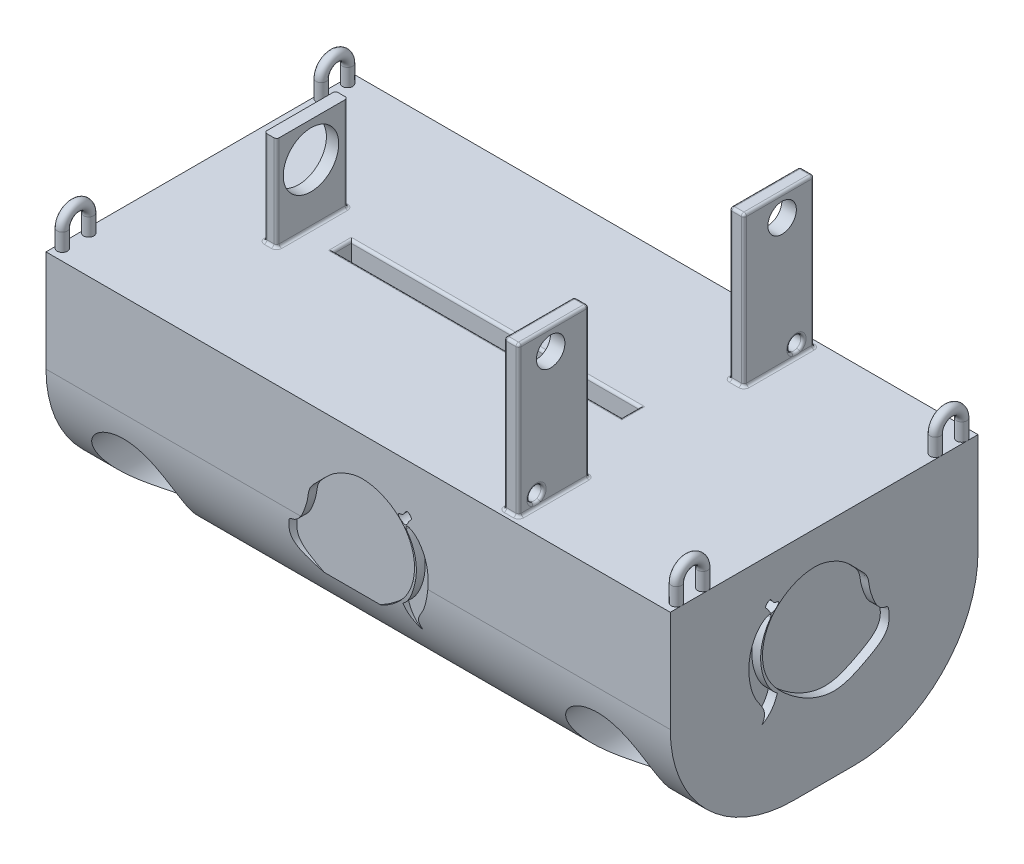
SolidWorks part; units mm, degrees
ref_plane "Front Plane" through (0, 0, 0) normal (0, 0, 1) x (1, 0, 0)
ref_plane "Top Plane" through (0, 0, 0) normal (0, 1, 0) x (1, 0, 0)
ref_plane "Right Plane" through (0, 0, 0) normal (1, 0, 0) x (0, 0, -1)
sketch "Sketch1" plane through (0, 0, 0) normal (0, 0, 1) x (1, 0, 0)
  line L0 (-32.1746, 8.1788) -> (-32.1746, -24.2661)
  line L1 (-32.1746, 8.1788) -> (57.9954, 8.1788)
  line L2 (-32.1746, -24.2661) -> (57.9954, -24.2661)
  line L3 (57.9954, 8.1788) -> (57.9954, -24.2661)
  dimension "D1" = 90.17
extrude "Boss-Extrude1" add sketch "Sketch1" along normal blind 44.45
sketch "Sketch2" plane through (0, 0, 0) normal (0, 0, -1) x (-1, 0, 0)
  line L4 (-12.9104, 8.1788) -> (-12.9104, -24.2661)
  line L8 (32.1746, 8.1788) -> (-57.9954, 8.1788)
  line L9 (-57.9954, 8.1788) -> (-57.9954, -24.2661)
  line L10 (-57.9954, -24.2661) -> (32.1746, -24.2661)
  line L11 (32.1746, -24.2661) -> (32.1746, 8.1788)
  line L12 (32.1746, 8.1788) -> (-57.9954, 8.1788)
  line L13 (-57.9954, 8.1788) -> (-57.9954, -24.2661)
  line L14 (-57.9954, -24.2661) -> (32.1746, -24.2661)
  line L15 (32.1746, -24.2661) -> (32.1746, 8.1788)
  circle A0 centre (-47.1378, -16.2985) radius 6.35
  circle A1 centre (21.317, -16.2985) radius 6.35
  dimension "D1" = 0
extrude "Cut-Extrude1" cut sketch "Sketch2" against normal blind 44.45 contours A0 | A1
sketch "Sketch4" plane through (57.9954, 0, 0) normal (1, 0, 0) x (0, 0, -1)
  line L0 (-42.8309, 10.7188) -> (-42.8309, 8.1788)
  line L2 (-42.8309, 10.7188) -> (-39.0209, 10.7188)
  line L3 (-39.0209, 10.7188) -> (-39.0209, 8.1788)
  line L4 (-44.45, 8.1788) -> (0, 8.1788) construction
  line L5 (-39.0209, 8.1788) -> (-39.0209, 10.7188)
  arc A0 (-39.0209, 10.7188) -> (-42.8309, 10.7188) centre (-40.9259, 10.7188) ccw
  dimension "D1" = 3.81
  dimension "D2" = 2.54
ref_plane "Plane2" through (0, 8.1788, 0) normal (0, 1, 0) x (1, 0, 0)
sketch "Sketch6" plane through (0, 8.1788, 0) normal (0, 1, 0) x (1, 0, 0)
  point P0 (57.9954, -39.0209)
sketch "Sketch13" plane through (0, 8.1788, 0) normal (0, 1, 0) x (1, 0, 0)
  circle A1 centre (57.2612, -39.0209) radius 0.7342
sweep "Sweep6" add profiles "Sketch13" path "Sketch4"
sketch "Sketch8" plane through (0, 8.1788, 0) normal (0, 1, 0) x (1, 0, 0)
  line L0 (12.9104, -44.45) -> (12.9104, 0) construction
  line L1 (57.9954, -44.45) -> (-32.1746, -44.45) construction
  line L2 (57.9954, 0) -> (-32.1746, 0) construction
  line L3 (12.9104, 0) -> (-32.1746, -22.225) construction
  line L4 (-32.1746, -44.45) -> (-32.1746, 0) construction
  line L5 (-32.1746, -22.225) -> (57.9954, -19.5104) construction
  line L6 (57.9954, -39.0209) -> (57.9954, 0) construction
sketch "Sketch9" plane through (57.9954, 0, 0) normal (1, 0, 0) x (0, 0, -1)
  line L0 (-20.1519, 8.3228) -> (-44.45, -8.6466) construction
  line L1 (-44.45, -24.2661) -> (-44.45, 8.1788) construction
  line L2 (-44.45, -8.6466) -> (-19.5104, 8.1788) construction
  line L3 (-39.0209, 8.1788) -> (0, 8.1788) construction
  line L4 (-19.5104, 8.1788) -> (-19.5104, -10.6637) construction
sketch "Sketch10" plane through (-32.1746, 0, 0) normal (-1, 0, 0) x (0, 0, 1)
  line L0 (44.45, -24.2661) -> (0, -24.2661) construction
  line L1 (44.45, -24.2661) -> (0, -24.2661)
  line L2 (22.225, -24.2661) -> (22.225, 18.16)
surface "Surface-Extrude1" sketch "Sketch10" parameters "D1"=44.45
ref_plane "Plane5" through (0, 0, 22.225) normal (0, 0, 1) x (1, 0, 0)
sketch "Sketch12" plane through (0, 8.1788, 0) normal (0, 1, 0) x (1, 0, 0)
  line L0 (12.9104, -44.45) -> (12.9104, 0)
surface "Surface-Extrude2" sketch "Sketch12" parameters "D1"=44.45
ref_plane "Plane6" through (12.9104, 0, 0) normal (1, 0, 0) x (0, 0, -1)
mirror "Mirror3" about plane through (12.9104, 0, 0) normal (1, 0, 0) of "Sweep6"
mirror "Mirror4" about plane through (0, 0, 22.225) normal (0, 0, 1) of "Mirror3", "Sweep6"
ref_plane "Plane7" through (-32.1746, -24.2661, 0) normal (0, 0, -1) x (-1, 0, 0)
sketch "Sketch15" plane through (0, 8.1788, 0) normal (0, 1, 0) x (1, 0, 0)
  line L0 (-32.1746, -22.225) -> (61.414, -22.225)
  line L1 (34.9575, -33.4196) -> (35.2115, -33.4196)
  line L2 (34.9575, -33.4196) -> (33.3724, -33.4196)
  line L3 (35.2115, -33.4196) -> (35.2115, -33.6736)
  line L4 (33.1184, -33.6736) -> (33.1184, -43.3256)
  line L6 (33.3724, -43.5796) -> (34.9575, -43.5796)
  line L7 (35.2115, -43.3256) -> (35.2115, -33.6736)
  line L8 (33.3724, -33.4196) -> (33.1184, -33.4196)
  line L9 (33.1184, -33.4196) -> (33.1184, -33.6736)
  line L10 (33.1184, -43.3256) -> (33.1184, -43.5796)
  line L11 (33.1184, -43.5796) -> (33.3724, -43.5796)
  line L12 (34.9575, -43.5796) -> (35.2115, -43.5796)
  line L13 (35.2115, -43.5796) -> (35.2115, -43.3256)
extrude "Boss-Extrude2" add sketch "Sketch15" along normal blind 21.59
fillet "Fillet2" radius 0.381 8 edges at (34.165, 29.7688, 33.4196) (34.165, 29.7688, 43.5796) (33.1184, 29.7688, 38.4996) (33.1184, 18.9738, 43.5796) (35.2115, 29.7688, 38.4996) (35.2115, 18.9738, 43.5796) (35.2115, 18.9738, 33.4196) (33.1184, 18.9738, 33.4196)
fillet "Fillet3" radius 0.381 8 edges at (35.0999, 8.1788, 43.468) (34.165, 8.1788, 43.5796) (33.23, 8.1788, 43.468) (35.2115, 8.1788, 38.4996) (33.1184, 8.1788, 38.4996) (33.23, 8.1788, 33.5312) (35.0999, 8.1788, 33.5312) (34.165, 8.1788, 33.4196)
mirror "Mirror5" about plane through (0, 0, 22.225) normal (0, 0, 1) of "Fillet2", "Boss-Extrude2"
sketch "Sketch16" plane through (0, 8.1788, 0) normal (0, 1, 0) x (1, 0, 0)
  line L0 (-32.1746, -22.225) -> (59.5851, -22.225)
  line L1 (30.0441, -20.955) -> (30.0441, -23.495)
  line L2 (30.0441, -23.495) -> (-11.5686, -23.495)
  line L3 (-11.5686, -23.495) -> (-11.5686, -20.955)
  line L4 (30.0441, -20.955) -> (-11.5686, -20.955)
  point P8 (30.0441, -22.225)
  point P9 (-11.5686, -22.225)
  dimension "D1" = 1.27
extrude "Cut-Extrude2" cut sketch "Sketch16" against normal blind 49.53 contours L1 L4 L3 L0 | L3 L2 L1 L0
fillet "Fillet4" radius 0.381 8 edges at (35.0999, 8.1788, 10.9188) (34.165, 8.1788, 11.0304) (33.23, 8.1788, 10.9188) (33.1184, 8.1788, 5.9504) (33.23, 8.1788, 0.982) (34.165, 8.1788, 0.8704) (35.0999, 8.1788, 0.982) (35.2115, 8.1788, 5.9504)
ref_plane "Plane8" through (35.2115, 0, 0) normal (1, 0, 0) x (0, 0, -1)
sketch "Sketch17" plane through (35.2115, 0, 0) normal (1, 0, 0) x (0, 0, -1)
  circle A0 centre (-5.5118, 26.67) radius 2.0574
  circle A1 centre (-38.9382, 26.67) radius 2.0574
extrude "Cut-Extrude3" cut sketch "Sketch17" against normal blind 49.53
sketch "Sketch18" plane through (35.2115, 0, 0) normal (1, 0, 0) x (0, 0, -1)
  line L0 (-43.1986, 9.8265) -> (-1.2514, 9.8265)
  line L1 (-43.1986, 29.3878) -> (-43.1986, 8.5598) construction
  line L2 (-1.2514, 8.5598) -> (-1.2514, 29.3878) construction
  line L4 (-22.225, 8.049) -> (-22.225, 11.9501)
  circle A0 centre (-3.4551, 9.8265) radius 1.0173
  circle A1 centre (-40.9949, 9.8265) radius 1.0173
extrude "Cut-Extrude4" cut sketch "Sketch18" against normal blind 49.53 contours A1 L0 | A1 L0 | L0 A0 | L0 A0
fillet "Fillet5" radius 0.381 4 edges at (35.2115, 9.8265, 39.9776) (33.1184, 9.8265, 39.9776) (33.1184, 9.8265, 4.4724) (35.2115, 9.8265, 2.4378)
fillet "Fillet8" radius 0.381 8 edges at (30.0441, -24.2661, 22.225) (9.2378, -24.2661, 23.495) (-11.5686, -24.2661, 22.225) (9.2378, -24.2661, 20.955) (30.0441, 8.1788, 22.225) (9.2378, 8.1788, 23.495) (-11.5686, 8.1788, 22.225) (9.2378, 8.1788, 20.955)
sketch "Sketch19" plane through (0, 8.1788, 0) normal (0, 1, 0) x (1, 0, 0)
  line L0 (-32.1746, -22.225) -> (-13.0525, -22.225)
  line L1 (-15.9561, -17.0826) -> (-15.9561, -27.3674)
  line L2 (-15.9561, -27.3674) -> (-17.7318, -27.3674)
  line L3 (-17.7318, -27.3674) -> (-17.7318, -17.0826)
  line L4 (-15.9561, -17.0826) -> (-17.7318, -17.0826)
  point P3 (-17.7318, -22.225)
  point P9 (-15.9561, -22.225)
extrude "Boss-Extrude3" add sketch "Sketch19" along normal blind 21.59 contours L1 L4 L3 L0 | L3 L2 L1 L0
fillet "Fillet9" radius 0.381 8 edges at (-16.844, 8.1788, 17.0826) (-17.7318, 8.1788, 22.225) (-16.844, 8.1788, 27.3674) (-15.9561, 8.1788, 22.225) (-15.9561, 18.9738, 27.3674) (-17.7318, 18.9738, 27.3674) (-15.9561, 18.9738, 17.0826) (-17.7318, 18.9738, 17.0826)
sketch "Sketch20" plane through (33.1184, 0, 0) normal (-1, 0, 0) x (0, 0, 1)
  circle A3 centre (22.3923, 16.779) radius 4.0028
extrude "Cut-Extrude5" cut sketch "Sketch20" along normal blind 69.85
sketch "Sketch21" plane through (-17.7318, 0, 0) normal (-1, 0, 0) x (0, 0, 1)
  line L0 (14.2037, 21.8308) -> (30.7917, 21.8308)
  line L1 (14.2037, 21.8308) -> (14.2037, 30.6759)
  line L2 (30.7917, 21.8308) -> (30.7917, 30.6759)
  line L3 (14.2037, 30.6759) -> (30.7917, 30.6759)
extrude "Cut-Extrude6" cut sketch "Sketch21" against normal blind 69.85
sketch "Sketch22" plane through (0, -24.2661, 0) normal (0, -1, 0) x (1, 0, 0)
  line L0 (-32.1746, 22.225) -> (57.9954, 22.225)
  line L1 (57.9954, 20.1519) -> (57.9954, 44.45) construction
  line L2 (57.9954, 22.225) -> (12.9104, 44.45)
  line L3 (12.9104, 44.45) -> (12.9104, 0)
  line L5 (20.5304, 14.605) -> (5.2904, 14.605)
  line L6 (20.5304, 14.605) -> (20.5304, 29.845)
  line L7 (20.5304, 29.845) -> (5.2904, 29.845)
  line L8 (5.2904, 14.605) -> (5.2904, 29.845)
  line L9 (20.5304, 14.605) -> (5.2904, 29.845) construction
  line L10 (20.5304, 29.845) -> (5.2904, 14.605) construction
  point P5 (12.9104, 22.225)
  line M3 (-11.9496, 23.876) -> (30.4251, 23.876)
  line M5 (30.4251, 20.574) -> (-11.9496, 20.574)
  dimension "D1" = 15.24
  dimension "D2" = 15.24
extrude "Cut-Extrude7" cut sketch "Sketch22" against normal blind 3.81 contours L5 L6 L3 M5 | L8 L5 L3 M5 | L8 L3 L7 M3 | L6 L7 L3 M3
sketch "Sketch24" plane through (0, 0, 44.45) normal (0, 0, 1) x (1, 0, 0)
  line L0 (-399.304, 232.8614) -> (-57.9707, 232.8614) construction
  spline S0 degree 3 poles (10.8399, 2.0421) (8.9502, 1.0814) (7.4886, -0.6147) (5.7708, -2.188) (5.6526, -3.8442) (5.1307, -5.5993) (4.3359, -7.3461) (2.8633, -7.5331) (2.7461, -8.732) (2.7587, -10.9084) (6.2142, -12.8758) (11.0129, -15.1887) (17.1594, -12.1936) (21.6518, -7.0039) (20.5877, 0.6419) (14.3612, 3.3669) (10.8399, 2.0421) (8.9502, 1.0814) (7.4886, -0.6147) knots -0.211382 -0.056837 -0.02752 0 0.061316 0.098937 0.124607 0.150682 0.206166 0.212473 0.228098 0.261144 0.337399 0.420477 0.559501 0.677874 0.788618 0.943163 0.97248 1 1.061316 1.098937 1.124607 only from (9.5285, 1.3112) to (9.5285, 1.3112)
  spline S1 degree 3 poles (19.8956, -0.5682) (18.1723, 1.0277) (19.5708, 0.9529) (19.8143, 2.2092) (20.8593, 1.1464) (20.1177, 0.6771) (19.8956, -0.5682) (18.1723, 1.0277) (19.5708, 0.9529) knots -0.527556 -0.432913 -0.259318 0 0.118391 0.301312 0.472444 0.567087 0.740682 1 1.118391 1.301312 1.472444 only from (18.7324, 0.8965) to (18.7324, 0.8965)
  spline S2 degree 2 poles (18.907, -10.4411) (19.4896, -12.3817) (21.144, -13.3342) knots 0 0 0 1 1 1
  spline S3 degree 3 poles (19.9917, 0) (20.8699, -0.2169) (22.269, -1.596) (23.1224, -4.3468) (22.988, -7.3194) (21.9588, -10.3306) (20.238, -11.9222) (21.144, -13.3342) knots 0 0 0 0 0.176751 0.372486 0.562263 0.767012 1 1 1 1
  spline S4 degree 3 poles (18.907, -10.4411) (19.6843, -9.8995) (21.7009, -6.7734) (21.6424, -2.8841) (19.8604, -0.502) knots 0 0 0 0 0.26071 1 1 1 1
  spline S5 degree 2 poles (19.8604, -0.502) (19.7179, -0.2059) (19.9917, 0) knots 0 0 0 1 1 1
extrude "Cut-Extrude8" cut sketch "Sketch24" against normal blind 1.27
mirror "Mirror6" about plane through (0, 0, 22.225) normal (0, 0, 1) of "Cut-Extrude8"
sketch "Sketch25" plane through (-32.1746, 0, 0) normal (-1, 0, 0) x (0, 0, 1)
  spline S0 degree 3 poles (20.9132, 2.8212) (19.0236, 1.8604) (17.562, 0.1643) (15.8441, -1.409) (15.7259, -3.0652) (15.204, -4.8203) (14.4092, -6.567) (12.9366, -6.754) (12.8194, -7.953) (12.8321, -10.1294) (16.2875, -12.0968) (21.0863, -14.4097) (27.2327, -11.4145) (31.7251, -6.2248) (30.6611, 1.4209) (24.4346, 4.146) (20.9132, 2.8212) (19.0236, 1.8604) (17.562, 0.1643) knots -0.211382 -0.056837 -0.02752 0 0.061316 0.098937 0.124607 0.150682 0.206166 0.212473 0.228098 0.261144 0.337399 0.420477 0.559501 0.677874 0.788618 0.943163 0.97248 1 1.061316 1.098937 1.124607 only from (19.6019, 2.0902) to (19.6019, 2.0902)
  spline S1 degree 3 poles (29.969, 0.2109) (28.2457, 1.8067) (29.6441, 1.732) (29.8876, 2.9883) (30.9326, 1.9254) (30.1911, 1.4561) (29.969, 0.2109) (28.2457, 1.8067) (29.6441, 1.732) knots -0.527556 -0.432913 -0.259318 0 0.118391 0.301312 0.472444 0.567087 0.740682 1 1.118391 1.301312 1.472444 only from (28.8058, 1.6756) to (28.8058, 1.6756)
  spline S2 degree 2 poles (28.9804, -9.662) (29.563, -11.6027) (31.2174, -12.5551) knots 0 0 0 1 1 1
  spline S3 degree 3 poles (30.0651, 0.779) (30.9432, 0.5622) (32.3424, -0.817) (33.1958, -3.5677) (33.0613, -6.5404) (32.0321, -9.5516) (30.3113, -11.1431) (31.2174, -12.5551) knots 0 0 0 0 0.176751 0.372486 0.562263 0.767012 1 1 1 1
  spline S4 degree 3 poles (28.9804, -9.662) (29.7577, -9.1205) (31.7743, -5.9944) (31.7158, -2.105) (29.9337, 0.277) knots 0 0 0 0 0.26071 1 1 1 1
  spline S5 degree 2 poles (29.9337, 0.277) (29.7913, 0.5731) (30.0651, 0.779) knots 0 0 0 1 1 1
extrude "Cut-Extrude9" cut sketch "Sketch25" against normal blind 1.27
mirror "Mirror7" about plane through (12.9104, 0, 0) normal (1, 0, 0) of "Cut-Extrude9"
fillet "Fillet10" radius 17.78 2 edges at (12.9104, -24.2661, 0) (12.9104, -24.2661, 44.45)
